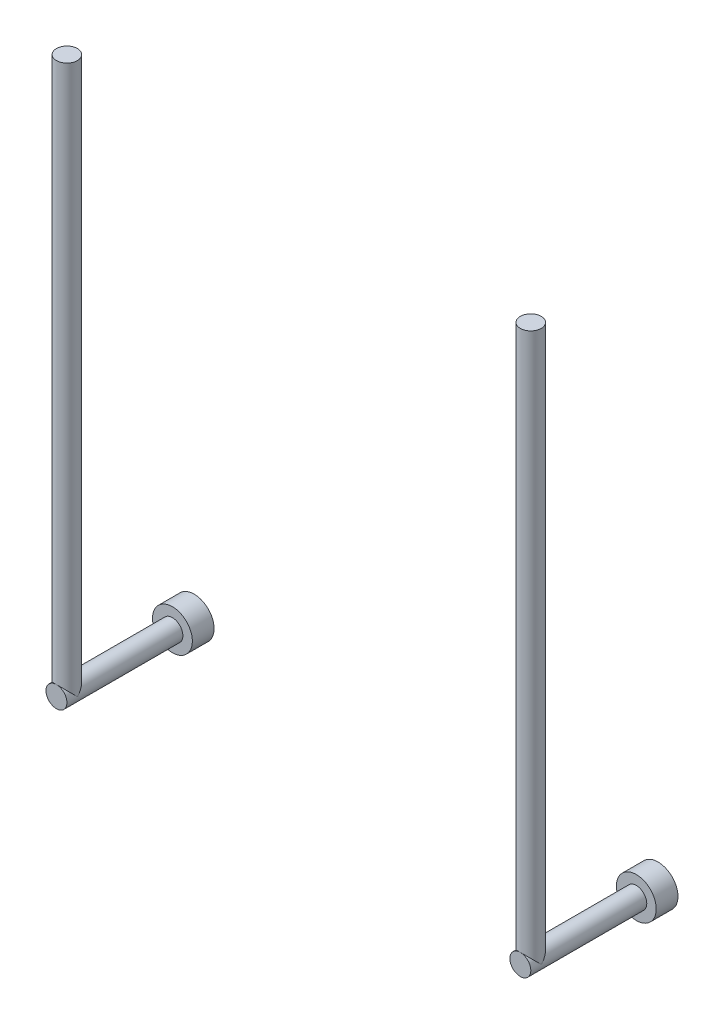
SolidWorks part; units mm, degrees
ref_plane "Front Plane" through (0, 0, 0) normal (0, 0, 1) x (1, 0, 0)
ref_plane "Top Plane" through (0, 0, 0) normal (0, 1, 0) x (1, 0, 0)
ref_plane "Right Plane" through (0, 0, 0) normal (1, 0, 0) x (0, 0, -1)
ref_plane "PY14_3" through (0, 0, 14.3) normal (0, 0, 1) x (1, 0, 0)
sketch "Sketch1" plane through (0, 0, 14.3) normal (0, 0, 1) x (1, 0, 0)
  circle A0 centre (-32, -20) radius 2.75
extrude "Bolt Head -32" add sketch "Sketch1" along normal blind 3 separate body
ref_plane "PY15_31" through (0, 0, 15.31) normal (0, 0, 1) x (1, 0, 0)
sketch "Sketch2" plane through (0, 0, 15.31) normal (0, 0, 1) x (1, 0, 0)
  circle A0 centre (-32, -20) radius 1.4438
extrude "Key Short Arm -32" add sketch "Sketch2" along normal blind 17.99 separate body
ref_plane "PZm20" through (0, -20, 0) normal (0, 1, 0) x (1, 0, 0)
sketch "Sketch3" plane through (0, -20, 0) normal (0, 1, 0) x (1, 0, 0)
  circle A0 centre (-32, -31.8562) radius 1.4438
extrude "Key Long Arm -32" add sketch "Sketch3" along normal blind 76 separate body
sketch "Sketch4" plane through (0, 0, 14.3) normal (0, 0, 1) x (1, 0, 0)
  circle A0 centre (32, -20) radius 2.75
extrude "Bolt Head +32" add sketch "Sketch4" along normal blind 3 separate body
sketch "Sketch5" plane through (0, 0, 15.31) normal (0, 0, 1) x (1, 0, 0)
  circle A0 centre (32, -20) radius 1.4438
extrude "Key Short Arm +32" add sketch "Sketch5" along normal blind 17.99 separate body
sketch "Sketch6" plane through (0, -20, 0) normal (0, 1, 0) x (1, 0, 0)
  circle A0 centre (32, -31.8562) radius 1.4438
extrude "Key Long Arm +32" add sketch "Sketch6" along normal blind 76 separate body
